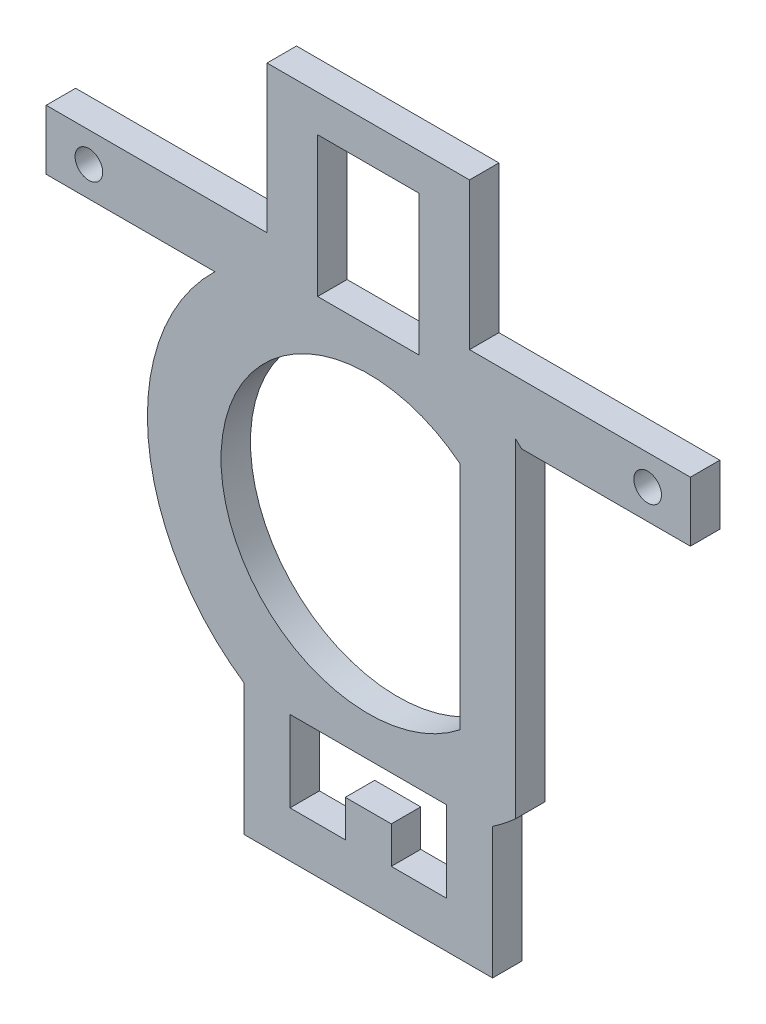
SolidWorks part; units mm, degrees
ref_plane "Front Plane" through (0, 0, 0) normal (0, 0, 1) x (1, 0, 0)
ref_plane "Top Plane" through (0, 0, 0) normal (0, 1, 0) x (1, 0, 0)
ref_plane "Right Plane" through (0, 0, 0) normal (1, 0, 0) x (0, 0, -1)
sketch "Sketch1" plane through (0, 0, 0) normal (0, 0, 1) x (1, 0, 0)
  line L0 (0, 14.47) -> (0, -49038.5432) construction
  line L1 (2.75, 14.4577) -> (-2.75, 14.4577) construction
  line L2 (2.75, -10.2577) -> (-2.75, -10.2577) construction
  line L3 (-5.5, 10.6654) -> (-5.5, 19.87)
  line L4 (-5.5, 19.87) -> (5.5, 19.87)
  line L5 (5.5, 19.87) -> (5.5, 10.6654)
  line L6 (-5.5, 17.87) -> (5.5, 17.87)
  line L7 (2.75, 14.4577) -> (2.75, 10.2577) construction
  line L8 (-2.75, 14.4577) -> (-2.75, 10.2577) construction
  line L9 (2.75, 10.2577) -> (-2.75, 10.2577) construction
  line L10 (2.75, 17.87) -> (2.75, 10.2577)
  line L11 (7.99, -8.9532) -> (7.99, 8.9532)
  line L12 (-2.75, 17.87) -> (-2.75, 10.2577)
  line L13 (2.75, 10.2577) -> (-2.75, 10.2577)
  line L14 (4.99, -6.253) -> (4.99, 6.253)
  line L15 (-1.25, -14.5549) -> (-1.25, -12.5549)
  line L16 (-4.2545, -14.5549) -> (-4.2545, -10.1549)
  line L17 (4.2545, -10.1549) -> (-4.2545, -10.1549)
  line L18 (4.2545, -14.5549) -> (4.2545, -10.1549)
  line L19 (4.2545, -14.5549) -> (-4.2545, -14.5549)
  line L20 (6.7545, -17.0549) -> (6.7545, -9.9185)
  line L21 (6.7545, -17.0549) -> (-6.7545, -17.0549)
  line L22 (-6.7545, -17.0549) -> (-6.7545, -9.9185)
  line L23 (-6.7545, -17.0549) -> (-6.7545, -10.1549) construction
  line L24 (6.7545, -17.0549) -> (6.7545, -10.1549) construction
  line L25 (-1.25, -12.5549) -> (1.25, -12.5549)
  line L26 (17.5, 8.6327) -> (-17.5, 8.6327)
  line L27 (17.5, 8.6327) -> (17.5, 11.8827)
  line L28 (17.5, 11.8827) -> (-17.5, 11.8827)
  line L29 (-17.5, 8.6327) -> (-17.5, 11.8827)
  line L30 (17.5, 8.6327) -> (-17.5, 11.8827) construction
  line L31 (17.5, 11.8827) -> (-17.5, 8.6327) construction
  line L32 (1.25, -14.5549) -> (1.25, -12.5549)
  line L34 (4.99, -8.9532) -> (4.99, 8.9532) construction
  circle A0 centre (0, 0) radius 8
  circle A1 centre (0, 0) radius 12
  circle A2 centre (-15.18, 10.2577) radius 0.75
  circle A3 centre (15.18, 10.2577) radius 0.75
  point P8 (0, 14.4577)
  point P11 (0, -10.2577)
  point P16 (0, 19.87)
  point P31 (0, 10.2577)
  point P40 (0, -14.5549)
  point P47 (0, -12.5549)
  dimension "D1" = 16
  dimension "D2" = 24
  dimension "D9" = 1.5
  dimension "D3" = 11
  dimension "D4" = 19.87
  dimension "D5" = 2
  dimension "D6" = 2.5
  dimension "D7" = 35
  dimension "D8" = 3.25
  dimension "D10" = 15.18
  dimension "D11" = 8.509
  dimension "D12" = 4.4
  dimension "D13" = 10.1549
  dimension "D14" = 2.5
  dimension "D15" = 2
  dimension "D16" = 7.99
  dimension "D17" = 3
extrude "Boss-Extrude1" add sketch "Sketch1" along normal blind 1.6 contours L3 L6 L5 L4 | A1 L22 L21 L20 L18 L19 L16 | L26 A1 L10 L13 L12 | A1 L3 L28 L29 L26 A2 | A1 L26 L27 L28 L5 A3 | A1 L5 L28 L10 | L28 L12 L6 L3 | L28 L5 L6 L10 | A1 L12 L28 L3 | L26 A1 L16 L17 L18 A0 | L19 L32 L25 L15 | L11 A0 L14 region at (-4.125, 14.8763, 0) region at (0, 18.87, 0) region at (-4.4841, 11.4931, 0) region at (-11.7764, 10.3428, 0) region at (-0.0154, 9.6704, 0) region at (4.125, 14.8763, 0) region at (-0.1726, 8.351, 0) region at (4.4841, 11.4931, 0) region at (11.7764, 10.3428, 0) region at (0, -14.6184, 0) region at (6.2154, 0, 0) region at (0, -13.5549, 0)
